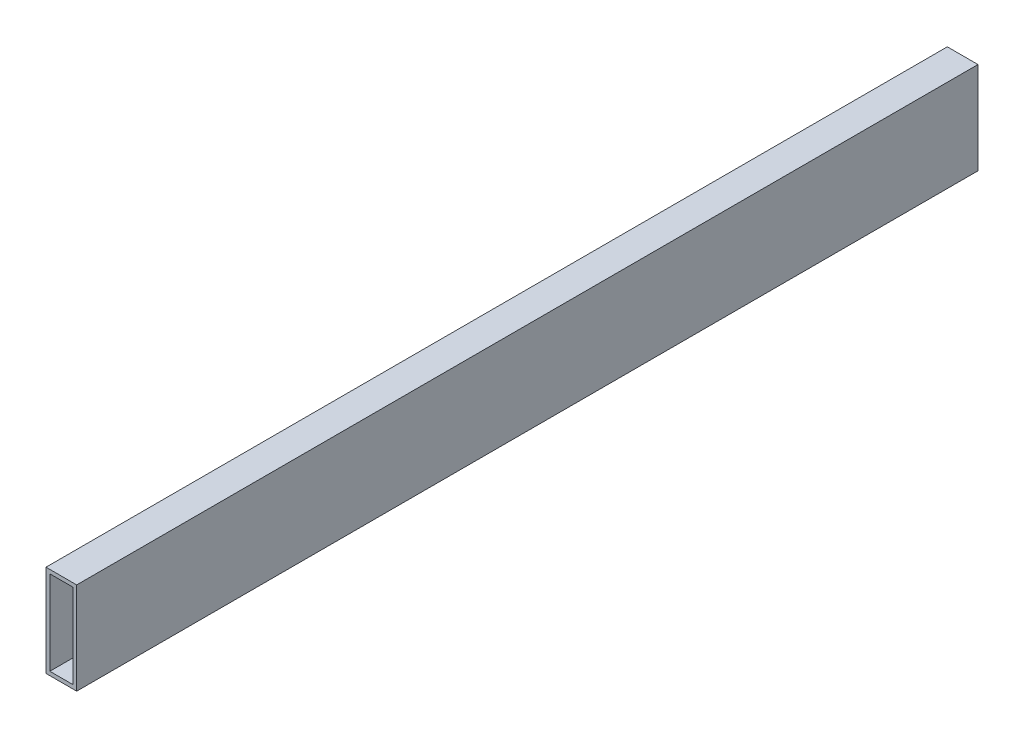
SolidWorks part; units mm, degrees
ref_plane "Front Plane" through (0, 0, 0) normal (0, 0, 1) x (1, 0, 0)
ref_plane "Top Plane" through (0, 0, 0) normal (0, 1, 0) x (1, 0, 0)
ref_plane "Right Plane" through (0, 0, 0) normal (1, 0, 0) x (0, 0, -1)
sketch "Sketch1" plane through (0, 0, 0) normal (0, 0, 1) x (1, 0, 0)
  line L1 (-12.7, -38.1) -> (12.7, -38.1)
  line L2 (-12.7, -38.1) -> (-12.7, 38.1)
  line L3 (-12.7, 38.1) -> (12.7, 38.1)
  line L4 (12.7, -38.1) -> (12.7, 38.1)
  line L5 (-12.7, -38.1) -> (12.7, 38.1) construction
  line L6 (-12.7, 38.1) -> (12.7, -38.1) construction
  point P0 (0, 0)
  dimension "D1" = 25.4
  dimension "D2" = 76.2
extrude "Boss-Extrude1" add sketch "Sketch1" along normal mid plane 745.998
shell "Shell1" thickness 3.175 removed face at (0, 0, -372.999) removed face at (0, 0, 372.999)
